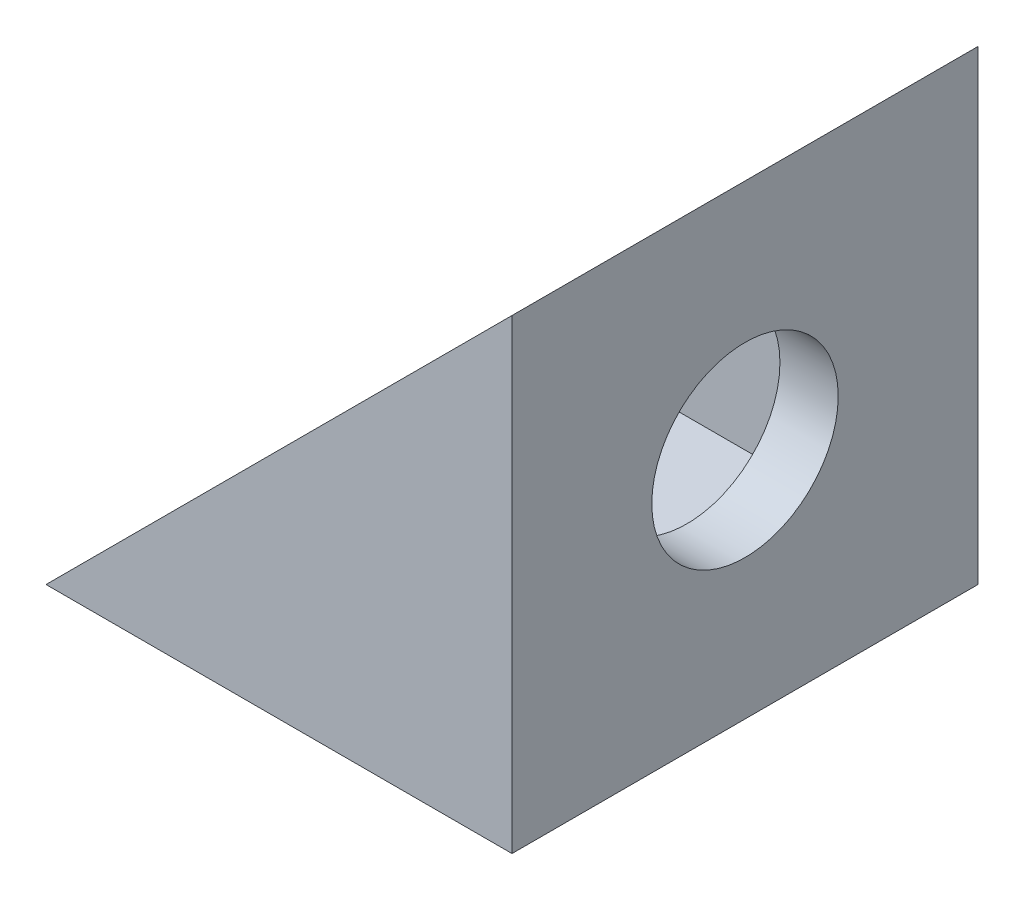
SolidWorks part; units mm, degrees
ref_plane "Front Plane" through (0, 0, 0) normal (0, 0, 1) x (1, 0, 0)
ref_plane "Top Plane" through (0, 0, 0) normal (0, 1, 0) x (1, 0, 0)
ref_plane "Right Plane" through (0, 0, 0) normal (1, 0, 0) x (0, 0, -1)
sketch "Sketch1" plane through (0, 0, 0) normal (0, 1, 0) x (1, 0, 0)
  line L1 (-10, 10) -> (10, 10)
  line L2 (-10, 10) -> (-10, -10)
  line L3 (-10, -10) -> (10, -10)
  line L4 (10, 10) -> (10, -10)
  line L5 (-10, 10) -> (10, -10) construction
  line L6 (-10, -10) -> (10, 10) construction
  point P0 (0, 0)
  dimension "D1" = 20
  dimension "D2" = 20
extrude "Boss-Extrude1" add sketch "Sketch1" along normal blind 20
sketch "Sketch2" plane through (0, 0, 10) normal (0, 0, 1) x (1, 0, 0)
  line L0 (-10, 0) -> (10, 20)
  line L1 (10, 20) -> (-10, 20)
  line L2 (-10, 20) -> (-10, 0)
extrude "Cut-Extrude1" cut sketch "Sketch2" against normal through all both and the other way through all
sketch "Sketch3" plane through (10, 0, 0) normal (1, 0, 0) x (0, 0, -1)
  line L0 (-10, 10) -> (10, 10) construction
  line L1 (-10, 20) -> (-10, 0) construction
  line L2 (10, 20) -> (10, 0) construction
  circle A0 centre (0, 10) radius 4
  dimension "D1" = 8
extrude "Cut-Extrude2" cut sketch "Sketch3" against normal through all contours A0
sketch "Sketch4" plane through (0, 0, 0) normal (0, -1, 0) x (1, 0, 0)
  circle A0 centre (0, 0) radius 4
  dimension "D1" = 8
extrude "Cut-Extrude3" cut sketch "Sketch4" against normal through all
ref_plane "Plane1" through (0, 20, 0) normal (0, 1, 0) x (1, 0, 0)
sketch "Sketch5" plane through (0, 20, 0) normal (0, 1, 0) x (1, 0, 0)
  line L1 (-7.5, -7.5) -> (7.5, -7.5)
  line L2 (-7.5, -7.5) -> (-7.5, 7.5)
  line L3 (-7.5, 7.5) -> (7.5, 7.5)
  line L4 (7.5, -7.5) -> (7.5, 7.5)
  line L5 (-7.5, -7.5) -> (7.5, 7.5) construction
  line L6 (-7.5, 7.5) -> (7.5, -7.5) construction
  point P0 (0, 0)
  dimension "D1" = 15
extrude "Cut-Extrude5" cut sketch "Sketch5" against normal offset from surface (17.5 mm away) 2.5 up to face at (0, 0, -4)
